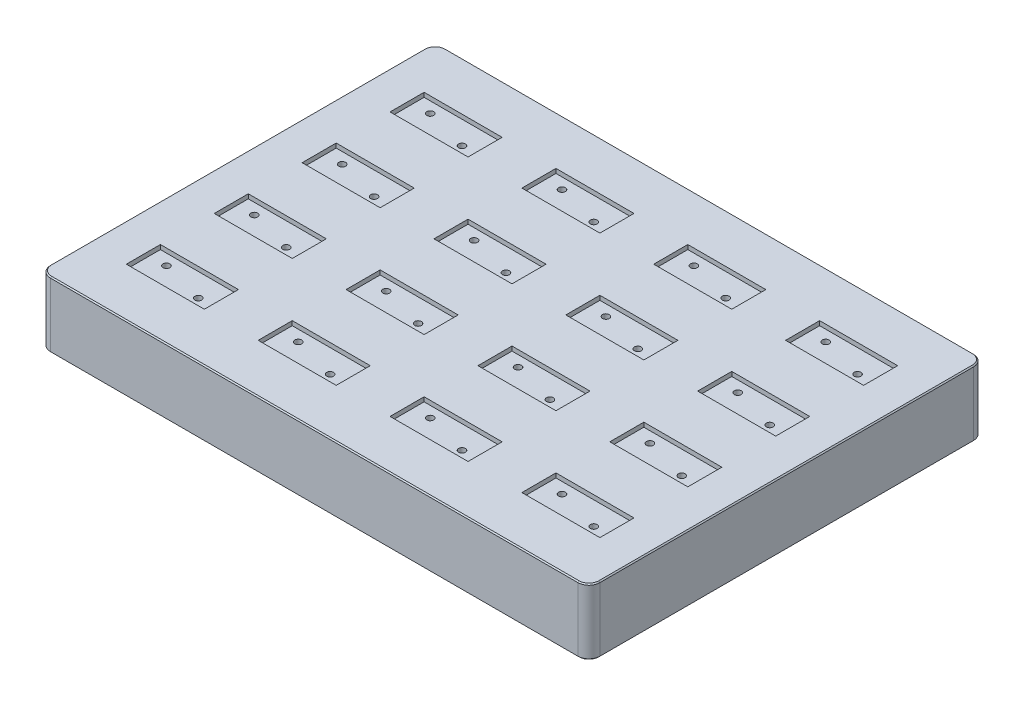
SolidWorks part; units mm, degrees
ref_plane "Front Plane" through (0, 0, 0) normal (0, 0, 1) x (1, 0, 0)
ref_plane "Top Plane" through (0, 0, 0) normal (0, 1, 0) x (1, 0, 0)
ref_plane "Right Plane" through (0, 0, 0) normal (1, 0, 0) x (0, 0, -1)
sketch "Sketch1" plane through (0, 0, 0) normal (0, 1, 0) x (1, 0, 0)
  line L1 (0, 0) -> (250, 0)
  line L2 (0, 0) -> (0, 180)
  line L3 (0, 180) -> (250, 180)
  line L4 (250, 0) -> (250, 180)
  dimension "D1" = 250
  dimension "D2" = 180
extrude "Boss-Extrude1" add sketch "Sketch1" along normal blind 30
sketch "Sketch2" plane through (0, 30, 0) normal (0, 1, 0) x (1, 0, 0)
  line L2 (0, 180) -> (0, 0) construction
  line L3 (17.25, 37.75) -> (52.75, 37.75)
  line L4 (17.25, 37.75) -> (17.25, 22.25)
  line L5 (17.25, 22.25) -> (52.75, 22.25)
  line L6 (52.75, 37.75) -> (52.75, 22.25)
  line L7 (0, 0) -> (250, 0) construction
  dimension "D1" = 15.5
  dimension "D2" = 35.5
  dimension "D3" = 17.25
  dimension "D4" = 22.25
extrude "Cut-Extrude1" cut sketch "Sketch2" against normal blind 2
pattern_linear "LPattern1" count 4 spacing 40 along (0, 0, -1) count 4 spacing 60 along (1, 0, 0) of "Cut-Extrude1"
sketch "Sketch3" plane through (0, 28, 0) normal (0, 1, 0) x (1, 0, 0)
  line L0 (35, 30) -> (35, 37.75) construction
  line L1 (52.75, 37.75) -> (17.25, 37.75) construction
  line L2 (52.75, 37.75) -> (17.25, 37.75) construction
  line L4 (17.25, 22.25) -> (52.75, 22.25) construction
  circle A0 centre (25, 32.75) radius 1.55
  circle A1 centre (45, 27.25) radius 1.55
  dimension "D1" = 3.1
  dimension "D2" = 20
  dimension "D3" = 5
  dimension "D4" = 5
  dimension "D5" = 10
extrude "Cut-Extrude2" cut sketch "Sketch3" against normal through all
pattern_linear "LPattern2" count 4 spacing 40 along (0, 0, -1) count 4 spacing 60 along (1, 0, 0) of "Cut-Extrude2"
sketch "Sketch4" plane through (0, 0, 0) normal (0, -1, 0) x (1, 0, 0)
  line L0 (0, -180) -> (0, 0) construction
  line L1 (3, -3) -> (247, -3)
  line L2 (3, -3) -> (3, -177)
  line L3 (3, -177) -> (247, -177)
  line L4 (247, -3) -> (247, -177)
  line L5 (250, -180) -> (0, -180) construction
  line L6 (250, 0) -> (250, -180) construction
  line L7 (0, 0) -> (250, 0) construction
  dimension "D1" = 3
  dimension "D2" = 3
  dimension "D3" = 3
  dimension "D4" = 3
extrude "Cut-Extrude3" cut sketch "Sketch4" against normal blind 21
fillet "Fillet1" radius 5 4 edges at (0, 15, -180) (0, 15, 0) (250, 15, 0) (250, 15, -180)
chamfer "Chamfer1" distance 0.5 angle 45 16 edges at (0, 0, -90) (1.4645, 0, -1.4645) (1.4645, 0, -178.5355) (125, 0, -180) (248.5355, 0, -1.4645) (248.5355, 0, -178.5355) (250, 0, -90) (0, 30, -90) (1.4645, 30, -1.4645) (1.4645, 30, -178.5355) (125, 30, 0) (125, 30, -180) (248.5355, 30, -1.4645) (248.5355, 30, -178.5355) (250, 30, -90) (125, 0, 0)
sketch "Sketch5" plane through (0, 0, -180) normal (0, 0, -1) x (-1, 0, 0)
  line L0 (0, 29.5) -> (0, 0.5) construction
  line L1 (-36.8, 5) -> (-24.3, 5)
  line L2 (-36.8, 5) -> (-36.8, 16.5)
  line L3 (-36.8, 16.5) -> (-24.3, 16.5)
  line L4 (-24.3, 5) -> (-24.3, 16.5)
  line L5 (-5, 0) -> (-245, 0) construction
  dimension "D1" = 12.5
  dimension "D2" = 11.5
  dimension "D3" = 24.3
  dimension "D4" = 5
extrude "Cut-Extrude4" cut sketch "Sketch5" against normal up to surface (3 mm away) up to face at (125, 10.5, -177)
fillet "Fillet2" radius 2 4 edges at (247, 10.5, -3) (247, 10.5, -177) (3, 10.5, -177) (3, 10.5, -3)
sketch "Sketch7" plane through (0, 21, 0) normal (0, -1, 0) x (1, 0, 0)
  line L0 (245, -180) -> (5, -180) construction
  line L1 (0, -175) -> (0, -5) construction
  circle A0 centre (17.78, -83.48) radius 3
  circle A1 centre (66.04, -77.13) radius 3
  circle A2 centre (60.96, -107.61) radius 3
  circle A3 centre (33.02, -107.61) radius 3
  circle A4 centre (17.78, -158.41) radius 3
  circle A5 centre (66.04, -159.68) radius 3
  dimension "D1" = 6
  dimension "D2" = 48.26
  dimension "D3" = 24.13
  dimension "D4" = 27.94
  dimension "D5" = 50.8
  dimension "D6" = 48.26
  dimension "D7" = 21.59
  dimension "D8" = 17.78
  dimension "D9" = 17.78
  dimension "D10" = 33.02
  dimension "D11" = 102.87
  dimension "D12" = 20.32
extrude "Boss-Extrude2" add sketch "Sketch7" along normal blind 3
fillet "Fillet3" radius 2 6 edges at (17.78, 21, -161.41) (66.04, 21, -162.68) (66.04, 21, -80.13) (60.96, 21, -110.61) (33.02, 21, -110.61) (17.78, 21, -86.48)
sketch "Sketch8" plane through (0, 18, 0) normal (0, -1, 0) x (1, 0, 0)
  circle A0 centre (17.78, -83.48) radius 1.3
  circle A1 centre (66.04, -77.13) radius 1.3
  circle A2 centre (60.96, -107.61) radius 1.3
  circle A3 centre (33.02, -107.61) radius 1.3
  circle A4 centre (17.78, -158.41) radius 1.3
  circle A5 centre (66.04, -159.68) radius 1.3
  dimension "D1" = 2.6
extrude "Cut-Extrude5" cut sketch "Sketch8" against normal blind 6
sketch "Sketch9" plane through (0, 0, -177) normal (0, 0, 1) x (1, 0, 0)
  line L4 (216.3, 17.35) -> (180.9, 17.35)
  line L5 (178.6349, 14.6506) -> (179.9697, 7.0806)
  line L6 (182.2348, 5.18) -> (214.9652, 5.18)
  line L7 (217.2303, 7.0806) -> (218.5651, 14.6506)
  circle A4 centre (222.1, 11.265) radius 1.6
  circle A5 centre (175.1, 11.265) radius 1.6
  arc A6 (180.9, 17.35) -> (178.6349, 14.6506) centre (180.9, 15.05) ccw
  arc A7 (179.9697, 7.0806) -> (182.2348, 5.18) centre (182.2348, 7.48) ccw
  arc A8 (214.9652, 5.18) -> (217.2303, 7.0806) centre (214.9652, 7.48) ccw
  arc A9 (218.5651, 14.6506) -> (216.3, 17.35) centre (216.3, 15.05) ccw
extrude "Cut-Extrude6" cut sketch "Sketch9" against normal up to surface (3 mm away) up to face at (30.55, 10.75, -180)
sketch "Sketch11" plane through (0, 21, 0) normal (0, -1, 0) x (1, 0, 0)
  line L0 (0.5, -90) -> (-8.3083, -90) construction
  line L1 (0.5, -5) -> (0.5, -175) construction
  line L2 (0, -175) -> (0, -5) construction
  line L3 (5, 0) -> (245, 0) construction
  line L4 (250, -5) -> (250, -175) construction
  line L5 (245, -180) -> (5, -180) construction
  line L6 (0, -90) -> (-6.231, -90) construction
  line L7 (125, 0) -> (125, 16.271) construction
  line L8 (125, -179.5) -> (125, -189.3502) construction
  line L9 (5, -179.5) -> (245, -179.5) construction
  circle A0 centre (5, -5) radius 5
  circle A1 centre (245, -5) radius 5
  circle A2 centre (245, -175) radius 5
  circle A3 centre (5, -175) radius 5
  circle A4 centre (125, -5) radius 5
  circle A5 centre (245, -90) radius 5
  circle A6 centre (5, -90) radius 5
  circle A7 centre (125, -175) radius 5
  dimension "D1" = 10
  dimension "D4" = 5
  dimension "D2" = 5
  dimension "D3" = 5
  dimension "D5" = 5
extrude "Boss-Extrude3" add sketch "Sketch11" along normal blind 19
